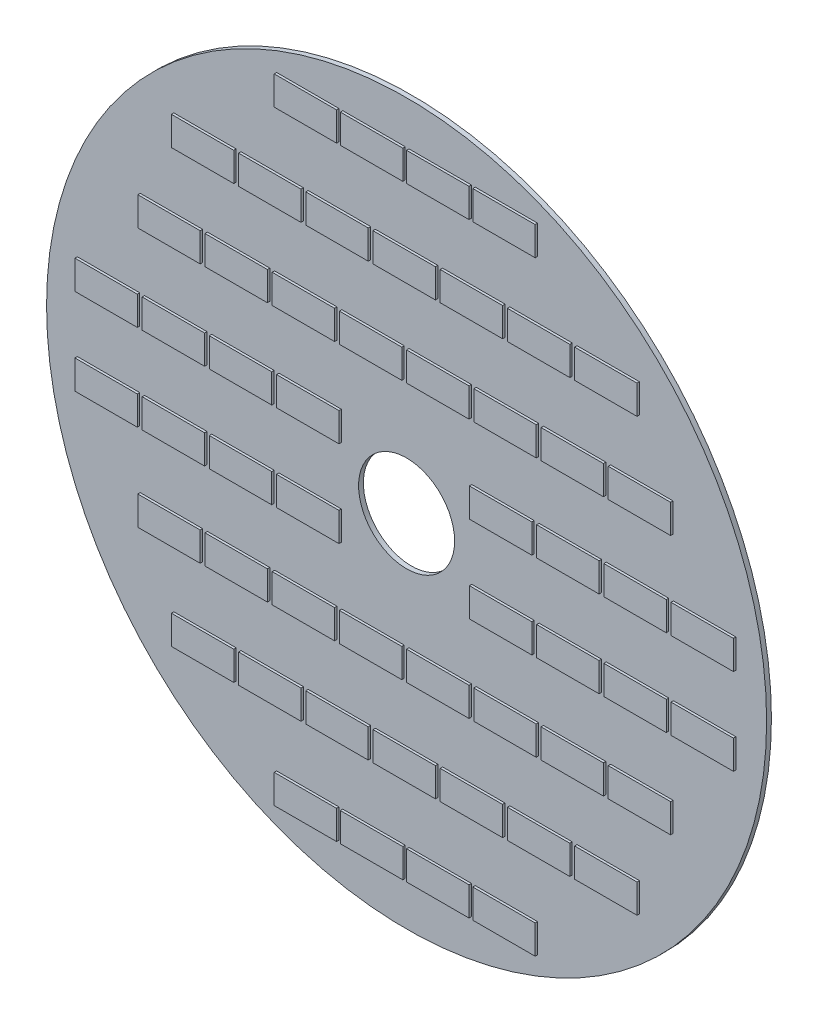
SolidWorks part; units mm, degrees
ref_plane "前视基准面" through (0, 0, 0) normal (0, 0, 1) x (1, 0, 0)
ref_plane "上视基准面" through (0, 0, 0) normal (0, 1, 0) x (1, 0, 0)
ref_plane "右视基准面" through (0, 0, 0) normal (1, 0, 0) x (0, 0, -1)
other "Configuration Table"
sketch "草图1" plane through (0, 0, 0) normal (0, 0, 1) x (1, 0, 0)
  line L5 (100, 90) -> (230, 90)
  line L6 (100, 90) -> (100, 30)
  line L8 (100, 30) -> (230, 30)
  line L12 (230, 90) -> (230, 30)
  line L14 (100, 90) -> (230, 30) construction
  line L18 (100, 30) -> (230, 90) construction
  line L24 (-1658.199, 0) -> (1658.199, 0) construction
  line L26 (0, 1113.9389) -> (0, -1113.9389) construction
  line L50 (300, 90) -> (430, 90)
  line L53 (300, 90) -> (300, 30)
  line L57 (300, 30) -> (430, 30)
  line L58 (430, 90) -> (430, 30)
  line L59 (300, 90) -> (430, 30) construction
  line L60 (300, 30) -> (430, 90) construction
  line L61 (37.3566, 180) -> (37.3566, 120)
  line L62 (237.3566, 120) -> (367.3566, 120)
  line L63 (237.3566, 180) -> (367.3566, 120) construction
  line L64 (37.3566, 120) -> (167.3566, 180) construction
  line L65 (237.3566, 180) -> (237.3566, 120)
  line L66 (367.3566, 180) -> (367.3566, 120)
  line L67 (37.3566, 180) -> (167.3566, 180)
  line L68 (37.3566, 180) -> (167.3566, 120) construction
  line L69 (237.3566, 180) -> (367.3566, 180)
  line L70 (237.3566, 120) -> (367.3566, 180) construction
  line L71 (37.3566, 120) -> (167.3566, 120)
  line L72 (167.3566, 180) -> (167.3566, 120)
  line L83 (37.3566, 364.2375) -> (37.3566, 304.2375)
  line L84 (237.3566, 304.2375) -> (367.3566, 304.2375)
  line L91 (133.7252, 270) -> (133.7252, 210)
  line L92 (333.7252, 210) -> (463.7252, 210)
  line L93 (333.7252, 270) -> (463.7252, 210) construction
  line L94 (133.7252, 210) -> (266.6142, 270) construction
  line L95 (333.7252, 270) -> (333.7252, 210)
  line L96 (463.7252, 270) -> (463.7252, 210)
  line L97 (133.7252, 270) -> (266.6142, 270)
  line L98 (133.7252, 270) -> (266.6142, 210) construction
  line L99 (333.7252, 270) -> (463.7252, 270)
  line L100 (333.7252, 210) -> (463.7252, 270) construction
  line L101 (133.7252, 210) -> (266.6142, 210)
  line L102 (266.6142, 270) -> (266.6142, 210)
  line L103 (-65, 274.2375) -> (-65, 210)
  line L104 (-65, 274.2375) -> (65, 274.2375)
  line L105 (-65, 210) -> (65, 210)
  line L106 (65, 274.2375) -> (65, 210)
  line L107 (-65, 210) -> (65, 274.2375) construction
  line L108 (-65, 274.2375) -> (65, 210) construction
  line L109 (-264.8303, 270) -> (-264.8303, 210)
  line L110 (-264.8303, 270) -> (-134.8303, 270)
  line L111 (-264.8303, 210) -> (-134.8303, 210)
  line L112 (-134.8303, 270) -> (-134.8303, 210)
  line L113 (-264.8303, 210) -> (-134.8303, 270) construction
  line L114 (-264.8303, 270) -> (-134.8303, 210) construction
  line L115 (-464.8303, 270) -> (-464.8303, 210)
  line L116 (-464.8303, 270) -> (-334.8303, 270)
  line L117 (-464.8303, 210) -> (-334.8303, 210)
  line L118 (-334.8303, 270) -> (-334.8303, 210)
  line L119 (-464.8303, 210) -> (-334.8303, 270) construction
  line L120 (-464.8303, 270) -> (-334.8303, 210) construction
  line L122 (237.3566, 364.2375) -> (237.3566, 304.2375)
  line L123 (367.3566, 364.2375) -> (367.3566, 304.2375)
  line L125 (37.3566, 364.2375) -> (167.3566, 364.2375)
  line L127 (237.3566, 364.2375) -> (367.3566, 364.2375)
  line L128 (37.3566, 304.2375) -> (167.3566, 304.2375)
  line L129 (167.3566, 364.2375) -> (167.3566, 304.2375)
  line L139 (237.3566, 364.2375) -> (367.3566, 304.2375) construction
  line L140 (37.3566, 304.2375) -> (167.3566, 364.2375) construction
  line L141 (37.3566, 364.2375) -> (167.3566, 304.2375) construction
  line L142 (237.3566, 304.2375) -> (367.3566, 364.2375) construction
  line L143 (37.3566, 450) -> (37.3566, 390)
  line L144 (237.3566, 390) -> (367.3566, 390)
  line L145 (237.3566, 450) -> (237.3566, 390)
  line L146 (367.3566, 450) -> (367.3566, 390)
  line L147 (37.3566, 450) -> (167.3566, 450)
  line L148 (237.3566, 450) -> (367.3566, 450)
  line L149 (37.3566, 390) -> (167.3566, 390)
  line L150 (167.3566, 450) -> (167.3566, 390)
  line L151 (237.3566, 450) -> (367.3566, 390) construction
  line L152 (37.3566, 390) -> (167.3566, 450) construction
  line L153 (37.3566, 450) -> (167.3566, 390) construction
  line L154 (237.3566, 390) -> (367.3566, 450) construction
  line L155 (37.3566, 535.7625) -> (37.3566, 475.7625)
  line L156 (237.3566, 475.7625) -> (367.3566, 475.7625)
  line L157 (237.3566, 535.7625) -> (237.3566, 475.7625)
  line L158 (367.3566, 535.7625) -> (367.3566, 475.7625)
  line L159 (37.3566, 535.7625) -> (167.3566, 535.7625)
  line L160 (237.3566, 535.7625) -> (367.3566, 535.7625)
  line L161 (37.3566, 475.7625) -> (167.3566, 475.7625)
  line L162 (167.3566, 535.7625) -> (167.3566, 475.7625)
  line L163 (237.3566, 535.7625) -> (367.3566, 475.7625) construction
  line L164 (37.3566, 475.7625) -> (167.3566, 535.7625) construction
  line L165 (37.3566, 535.7625) -> (167.3566, 475.7625) construction
  line L166 (237.3566, 475.7625) -> (367.3566, 535.7625) construction
  line L167 (-264.8303, 565.7625) -> (-134.8303, 625.7625) construction
  line L168 (133.7252, 565.7625) -> (266.6142, 565.7625)
  line L169 (-65, 565.7625) -> (65, 625.7625) construction
  line L170 (-65, 625.7625) -> (-65, 565.7625)
  line L171 (-264.8303, 625.7625) -> (-264.8303, 565.7625)
  line L172 (-134.8303, 625.7625) -> (-134.8303, 565.7625)
  line L173 (133.7252, 625.7625) -> (266.6142, 625.7625)
  line L174 (133.7252, 625.7625) -> (266.6142, 565.7625) construction
  line L175 (65, 625.7625) -> (65, 565.7625)
  line L176 (-264.8303, 625.7625) -> (-134.8303, 565.7625) construction
  line L177 (133.7252, 625.7625) -> (133.7252, 565.7625)
  line L178 (-65, 625.7625) -> (65, 625.7625)
  line L179 (-65, 565.7625) -> (65, 565.7625)
  line L180 (-264.8303, 565.7625) -> (-134.8303, 565.7625)
  line L181 (133.7252, 565.7625) -> (266.6142, 625.7625) construction
  line L182 (266.6142, 625.7625) -> (266.6142, 565.7625)
  line L183 (-264.8303, 625.7625) -> (-134.8303, 625.7625)
  line L184 (-65, 625.7625) -> (65, 565.7625) construction
  line L185 (-300, 90) -> (-300, 30)
  line L186 (-300, 30) -> (-430, 30)
  line L187 (-430, 90) -> (-430, 30)
  line L188 (-300, 90) -> (-430, 90)
  line L189 (-100, 30) -> (-230, 30)
  line L190 (-230, 90) -> (-230, 30)
  line L191 (-100, 90) -> (-230, 90)
  line L192 (-100, 90) -> (-100, 30)
  line L193 (-37.3566, 180) -> (-167.3566, 180)
  line L194 (-167.3566, 180) -> (-167.3566, 120)
  line L195 (-37.3566, 120) -> (-167.3566, 120)
  line L196 (-37.3566, 180) -> (-37.3566, 120)
  line L197 (-237.3566, 180) -> (-237.3566, 120)
  line L198 (-237.3566, 180) -> (-367.3566, 180)
  line L199 (-367.3566, 180) -> (-367.3566, 120)
  line L200 (-237.3566, 120) -> (-367.3566, 120)
  line L201 (-237.3566, 475.7625) -> (-367.3566, 535.7625) construction
  line L202 (-37.3566, 535.7625) -> (-167.3566, 475.7625) construction
  line L203 (-37.3566, 475.7625) -> (-167.3566, 535.7625) construction
  line L204 (-237.3566, 535.7625) -> (-367.3566, 475.7625) construction
  line L205 (-237.3566, 390) -> (-367.3566, 450) construction
  line L206 (-37.3566, 450) -> (-167.3566, 390) construction
  line L207 (-37.3566, 390) -> (-167.3566, 450) construction
  line L208 (-237.3566, 450) -> (-367.3566, 390) construction
  line L209 (-237.3566, 304.2375) -> (-367.3566, 364.2375) construction
  line L210 (-37.3566, 364.2375) -> (-167.3566, 304.2375) construction
  line L211 (-37.3566, 304.2375) -> (-167.3566, 364.2375) construction
  line L212 (-237.3566, 364.2375) -> (-367.3566, 304.2375) construction
  line L213 (-167.3566, 535.7625) -> (-167.3566, 475.7625)
  line L214 (-37.3566, 475.7625) -> (-167.3566, 475.7625)
  line L215 (-237.3566, 535.7625) -> (-367.3566, 535.7625)
  line L216 (-37.3566, 535.7625) -> (-167.3566, 535.7625)
  line L217 (-367.3566, 535.7625) -> (-367.3566, 475.7625)
  line L218 (-237.3566, 535.7625) -> (-237.3566, 475.7625)
  line L219 (-237.3566, 475.7625) -> (-367.3566, 475.7625)
  line L220 (-37.3566, 535.7625) -> (-37.3566, 475.7625)
  line L221 (-167.3566, 450) -> (-167.3566, 390)
  line L222 (-37.3566, 390) -> (-167.3566, 390)
  line L223 (-237.3566, 450) -> (-367.3566, 450)
  line L224 (-37.3566, 450) -> (-167.3566, 450)
  line L225 (-367.3566, 450) -> (-367.3566, 390)
  line L226 (-237.3566, 450) -> (-237.3566, 390)
  line L227 (-237.3566, 390) -> (-367.3566, 390)
  line L228 (-37.3566, 450) -> (-37.3566, 390)
  line L229 (-167.3566, 364.2375) -> (-167.3566, 304.2375)
  line L230 (-37.3566, 304.2375) -> (-167.3566, 304.2375)
  line L231 (-237.3566, 364.2375) -> (-367.3566, 364.2375)
  line L232 (-37.3566, 364.2375) -> (-167.3566, 364.2375)
  line L233 (-367.3566, 364.2375) -> (-367.3566, 304.2375)
  line L234 (-237.3566, 364.2375) -> (-237.3566, 304.2375)
  line L235 (-237.3566, 304.2375) -> (-367.3566, 304.2375)
  line L236 (-37.3566, 364.2375) -> (-37.3566, 304.2375)
  line L237 (-237.3566, -364.2375) -> (-367.3566, -304.2375) construction
  line L238 (-37.3566, -304.2375) -> (-167.3566, -364.2375) construction
  line L239 (-37.3566, -364.2375) -> (-167.3566, -304.2375) construction
  line L240 (-237.3566, -304.2375) -> (-367.3566, -364.2375) construction
  line L241 (-237.3566, -450) -> (-367.3566, -390) construction
  line L242 (-37.3566, -390) -> (-167.3566, -450) construction
  line L243 (-37.3566, -450) -> (-167.3566, -390) construction
  line L244 (-237.3566, -390) -> (-367.3566, -450) construction
  line L245 (-237.3566, -535.7625) -> (-367.3566, -475.7625) construction
  line L246 (-37.3566, -475.7625) -> (-167.3566, -535.7625) construction
  line L247 (-37.3566, -535.7625) -> (-167.3566, -475.7625) construction
  line L248 (-237.3566, -475.7625) -> (-367.3566, -535.7625) construction
  line L249 (-65, -625.7625) -> (65, -565.7625) construction
  line L250 (133.7252, -565.7625) -> (266.6142, -625.7625) construction
  line L251 (-264.8303, -625.7625) -> (-134.8303, -565.7625) construction
  line L252 (133.7252, -625.7625) -> (266.6142, -565.7625) construction
  line L253 (-65, -565.7625) -> (65, -625.7625) construction
  line L254 (-264.8303, -565.7625) -> (-134.8303, -625.7625) construction
  line L255 (237.3566, -475.7625) -> (367.3566, -535.7625) construction
  line L256 (37.3566, -535.7625) -> (167.3566, -475.7625) construction
  line L257 (37.3566, -475.7625) -> (167.3566, -535.7625) construction
  line L258 (237.3566, -535.7625) -> (367.3566, -475.7625) construction
  line L259 (237.3566, -390) -> (367.3566, -450) construction
  line L260 (37.3566, -450) -> (167.3566, -390) construction
  line L261 (37.3566, -390) -> (167.3566, -450) construction
  line L262 (237.3566, -450) -> (367.3566, -390) construction
  line L263 (237.3566, -304.2375) -> (367.3566, -364.2375) construction
  line L264 (37.3566, -364.2375) -> (167.3566, -304.2375) construction
  line L265 (37.3566, -304.2375) -> (167.3566, -364.2375) construction
  line L266 (237.3566, -364.2375) -> (367.3566, -304.2375) construction
  line L267 (-464.8303, -270) -> (-334.8303, -210) construction
  line L268 (-464.8303, -210) -> (-334.8303, -270) construction
  line L269 (-264.8303, -270) -> (-134.8303, -210) construction
  line L270 (-264.8303, -210) -> (-134.8303, -270) construction
  line L271 (-65, -274.2375) -> (65, -210) construction
  line L272 (-65, -210) -> (65, -274.2375) construction
  line L273 (333.7252, -210) -> (463.7252, -270) construction
  line L274 (133.7252, -270) -> (266.6142, -210) construction
  line L275 (133.7252, -210) -> (266.6142, -270) construction
  line L276 (333.7252, -270) -> (463.7252, -210) construction
  line L277 (237.3566, -120) -> (367.3566, -180) construction
  line L278 (37.3566, -180) -> (167.3566, -120) construction
  line L279 (37.3566, -120) -> (167.3566, -180) construction
  line L280 (237.3566, -180) -> (367.3566, -120) construction
  line L281 (300, -30) -> (430, -90) construction
  line L282 (300, -90) -> (430, -30) construction
  line L283 (100, -30) -> (230, -90) construction
  line L284 (100, -90) -> (230, -30) construction
  line L285 (-37.3566, -364.2375) -> (-37.3566, -304.2375)
  line L286 (-237.3566, -304.2375) -> (-367.3566, -304.2375)
  line L287 (-237.3566, -364.2375) -> (-237.3566, -304.2375)
  line L288 (-367.3566, -364.2375) -> (-367.3566, -304.2375)
  line L289 (-37.3566, -364.2375) -> (-167.3566, -364.2375)
  line L290 (-237.3566, -364.2375) -> (-367.3566, -364.2375)
  line L291 (-37.3566, -304.2375) -> (-167.3566, -304.2375)
  line L292 (-167.3566, -364.2375) -> (-167.3566, -304.2375)
  line L293 (-37.3566, -450) -> (-37.3566, -390)
  line L294 (-237.3566, -390) -> (-367.3566, -390)
  line L295 (-237.3566, -450) -> (-237.3566, -390)
  line L296 (-367.3566, -450) -> (-367.3566, -390)
  line L297 (-37.3566, -450) -> (-167.3566, -450)
  line L298 (-237.3566, -450) -> (-367.3566, -450)
  line L299 (-37.3566, -390) -> (-167.3566, -390)
  line L300 (-167.3566, -450) -> (-167.3566, -390)
  line L301 (-37.3566, -535.7625) -> (-37.3566, -475.7625)
  line L302 (-237.3566, -475.7625) -> (-367.3566, -475.7625)
  line L303 (-237.3566, -535.7625) -> (-237.3566, -475.7625)
  line L304 (-367.3566, -535.7625) -> (-367.3566, -475.7625)
  line L305 (-37.3566, -535.7625) -> (-167.3566, -535.7625)
  line L306 (-237.3566, -535.7625) -> (-367.3566, -535.7625)
  line L307 (-37.3566, -475.7625) -> (-167.3566, -475.7625)
  line L308 (-167.3566, -535.7625) -> (-167.3566, -475.7625)
  line L309 (-237.3566, -120) -> (-367.3566, -120)
  line L310 (-367.3566, -180) -> (-367.3566, -120)
  line L311 (-237.3566, -180) -> (-367.3566, -180)
  line L312 (-237.3566, -180) -> (-237.3566, -120)
  line L313 (-37.3566, -180) -> (-37.3566, -120)
  line L314 (-37.3566, -120) -> (-167.3566, -120)
  line L315 (-167.3566, -180) -> (-167.3566, -120)
  line L316 (-37.3566, -180) -> (-167.3566, -180)
  line L317 (-100, -90) -> (-100, -30)
  line L318 (-100, -90) -> (-230, -90)
  line L319 (-230, -90) -> (-230, -30)
  line L320 (-100, -30) -> (-230, -30)
  line L321 (-300, -90) -> (-430, -90)
  line L322 (-430, -90) -> (-430, -30)
  line L323 (-300, -30) -> (-430, -30)
  line L324 (-300, -90) -> (-300, -30)
  line L325 (-264.8303, -625.7625) -> (-134.8303, -625.7625)
  line L326 (266.6142, -625.7625) -> (266.6142, -565.7625)
  line L327 (-264.8303, -565.7625) -> (-134.8303, -565.7625)
  line L328 (-65, -565.7625) -> (65, -565.7625)
  line L329 (-65, -625.7625) -> (65, -625.7625)
  line L330 (133.7252, -625.7625) -> (133.7252, -565.7625)
  line L331 (65, -625.7625) -> (65, -565.7625)
  line L332 (133.7252, -625.7625) -> (266.6142, -625.7625)
  line L333 (-134.8303, -625.7625) -> (-134.8303, -565.7625)
  line L334 (-264.8303, -625.7625) -> (-264.8303, -565.7625)
  line L335 (-65, -625.7625) -> (-65, -565.7625)
  line L336 (133.7252, -565.7625) -> (266.6142, -565.7625)
  line L337 (167.3566, -535.7625) -> (167.3566, -475.7625)
  line L338 (37.3566, -475.7625) -> (167.3566, -475.7625)
  line L339 (237.3566, -535.7625) -> (367.3566, -535.7625)
  line L340 (37.3566, -535.7625) -> (167.3566, -535.7625)
  line L341 (367.3566, -535.7625) -> (367.3566, -475.7625)
  line L342 (237.3566, -535.7625) -> (237.3566, -475.7625)
  line L343 (237.3566, -475.7625) -> (367.3566, -475.7625)
  line L344 (37.3566, -535.7625) -> (37.3566, -475.7625)
  line L345 (167.3566, -450) -> (167.3566, -390)
  line L346 (37.3566, -390) -> (167.3566, -390)
  line L347 (237.3566, -450) -> (367.3566, -450)
  line L348 (37.3566, -450) -> (167.3566, -450)
  line L349 (367.3566, -450) -> (367.3566, -390)
  line L350 (237.3566, -450) -> (237.3566, -390)
  line L351 (237.3566, -390) -> (367.3566, -390)
  line L352 (37.3566, -450) -> (37.3566, -390)
  line L353 (167.3566, -364.2375) -> (167.3566, -304.2375)
  line L354 (37.3566, -304.2375) -> (167.3566, -304.2375)
  line L355 (237.3566, -364.2375) -> (367.3566, -364.2375)
  line L356 (37.3566, -364.2375) -> (167.3566, -364.2375)
  line L357 (367.3566, -364.2375) -> (367.3566, -304.2375)
  line L358 (237.3566, -364.2375) -> (237.3566, -304.2375)
  line L359 (-334.8303, -270) -> (-334.8303, -210)
  line L360 (-464.8303, -210) -> (-334.8303, -210)
  line L361 (-464.8303, -270) -> (-334.8303, -270)
  line L362 (-464.8303, -270) -> (-464.8303, -210)
  line L363 (-134.8303, -270) -> (-134.8303, -210)
  line L364 (-264.8303, -210) -> (-134.8303, -210)
  line L365 (-264.8303, -270) -> (-134.8303, -270)
  line L366 (-264.8303, -270) -> (-264.8303, -210)
  line L367 (65, -274.2375) -> (65, -210)
  line L368 (-65, -210) -> (65, -210)
  line L369 (-65, -274.2375) -> (65, -274.2375)
  line L370 (-65, -274.2375) -> (-65, -210)
  line L371 (266.6142, -270) -> (266.6142, -210)
  line L372 (133.7252, -210) -> (266.6142, -210)
  line L373 (333.7252, -270) -> (463.7252, -270)
  line L374 (133.7252, -270) -> (266.6142, -270)
  line L375 (463.7252, -270) -> (463.7252, -210)
  line L376 (333.7252, -270) -> (333.7252, -210)
  line L377 (333.7252, -210) -> (463.7252, -210)
  line L378 (133.7252, -270) -> (133.7252, -210)
  line L379 (237.3566, -304.2375) -> (367.3566, -304.2375)
  line L380 (37.3566, -364.2375) -> (37.3566, -304.2375)
  line L381 (167.3566, -180) -> (167.3566, -120)
  line L382 (37.3566, -120) -> (167.3566, -120)
  line L383 (237.3566, -180) -> (367.3566, -180)
  line L384 (37.3566, -180) -> (167.3566, -180)
  line L385 (367.3566, -180) -> (367.3566, -120)
  line L386 (237.3566, -180) -> (237.3566, -120)
  line L387 (237.3566, -120) -> (367.3566, -120)
  line L388 (37.3566, -180) -> (37.3566, -120)
  line L389 (430, -90) -> (430, -30)
  line L390 (300, -30) -> (430, -30)
  line L391 (300, -90) -> (300, -30)
  line L392 (300, -90) -> (430, -90)
  line L393 (230, -90) -> (230, -30)
  line L394 (100, -30) -> (230, -30)
  line L395 (100, -90) -> (100, -30)
  line L396 (100, -90) -> (230, -90)
  line L397 (-65, 715.7625) -> (65, 715.7625)
  line L398 (-65, 715.7625) -> (65, 655.7625) construction
  line L399 (65, 715.7625) -> (65, 655.7625)
  line L400 (-65, 655.7625) -> (65, 715.7625) construction
  line L401 (-65, 715.7625) -> (-65, 655.7625)
  line L402 (-65, 655.7625) -> (65, 655.7625)
  line L403 (-65, -655.7625) -> (65, -715.7625) construction
  line L404 (-65, -715.7625) -> (65, -655.7625) construction
  line L405 (-65, -655.7625) -> (65, -655.7625)
  line L406 (-65, -715.7625) -> (-65, -655.7625)
  line L407 (65, -715.7625) -> (65, -655.7625)
  line L408 (-65, -715.7625) -> (65, -715.7625)
  circle A0 centre (0, 0) radius 750 construction
  point P0 (165, 60)
  point P5 (102.3566, 150)
  point P7 (365, 60)
  point P16 (302.3566, 192.8005)
  point P24 (200.1697, 595.7625)
  point P26 (200.1697, 240)
  point P29 (102.3566, 334.2375)
  point P39 (102.3566, 420)
  point P47 (0, 274.2375)
  point P70 (102.3566, 505.7625)
  point P80 (302.3566, 462.8005)
  point P81 (302.3566, 377.038)
  point P132 (-102.3566, 505.7625)
  point P133 (-102.3566, 420)
  point P134 (-102.3566, 334.2375)
  point P247 (-102.3566, -334.2375)
  point P248 (-102.3566, -420)
  point P249 (-102.3566, -505.7625)
  point P250 (102.3566, -505.7625)
  point P251 (102.3566, -420)
  point P252 (102.3566, -334.2375)
  point P253 (200.1697, -240)
  point P254 (200.1697, -595.7625)
  point P255 (302.3566, -192.8005)
  point P256 (365, -60)
  point P257 (102.3566, -150)
  point P258 (165, -60)
  dimension "D3" = 100
  dimension "D1" = 2
  dimension "D2" = 30
  dimension "D4" = 30
  dimension "D5" = 60
  dimension "D6" = 130
  dimension "D7" = 70
  dimension "D8" = 70
  dimension "D9" = 2
  dimension "D10" = 3
  dimension "D11" = 130
  dimension "D12" = 60
  dimension "D13" = 30
  dimension "D14" = 60
  dimension "D15" = 30
sketch "草图2" plane through (0, 0, 0) normal (0, 0, 1) x (1, 0, 0)
  circle A0 centre (0, 0) radius 750
  circle A1 centre (0, 0) radius 100
  dimension "D1" = 1500
  dimension "D2" = 200
extrude "凸台-拉伸1" add sketch "草图2" along normal blind 10
sketch "草图3" plane through (0, 0, 0) normal (0, 0, 1) x (1, 0, 0)
  line L0 (-1673.2224, 0) -> (1673.2224, 0) construction
  line L2 (135.9057, 120) -> (265.9057, 120)
  line L3 (0, -869.8968) -> (0, 1064.1184) construction
  line L4 (135.9057, 120) -> (135.9057, 60)
  line L5 (135.9057, 60) -> (265.9057, 60)
  line L6 (265.9057, 120) -> (265.9057, 60)
  line L18 (275.9057, 120) -> (275.9057, 60)
  line L19 (275.9057, 120) -> (405.9057, 120)
  line L20 (405.9057, 120) -> (405.9057, 60)
  line L21 (275.9057, 60) -> (405.9057, 60)
  line L22 (415.9057, 120) -> (415.9057, 60)
  line L23 (415.9057, 120) -> (545.9057, 120)
  line L24 (545.9057, 120) -> (545.9057, 60)
  line L25 (415.9057, 60) -> (545.9057, 60)
  line L26 (555.9057, 120) -> (555.9057, 60)
  line L27 (555.9057, 120) -> (685.9057, 120)
  line L28 (685.9057, 120) -> (685.9057, 60)
  line L29 (555.9057, 60) -> (685.9057, 60)
  line L30 (145, 300) -> (145, 240)
  line L31 (-555.9057, 60) -> (-685.9057, 60)
  line L32 (-685.9057, 120) -> (-685.9057, 60)
  line L33 (-555.9057, 120) -> (-685.9057, 120)
  line L34 (-555.9057, 120) -> (-555.9057, 60)
  line L35 (-415.9057, 60) -> (-545.9057, 60)
  line L36 (-545.9057, 120) -> (-545.9057, 60)
  line L37 (-415.9057, 120) -> (-545.9057, 120)
  line L38 (-415.9057, 120) -> (-415.9057, 60)
  line L39 (-275.9057, 60) -> (-405.9057, 60)
  line L40 (-405.9057, 120) -> (-405.9057, 60)
  line L41 (-275.9057, 120) -> (-405.9057, 120)
  line L42 (-275.9057, 120) -> (-275.9057, 60)
  line L43 (-265.9057, 120) -> (-265.9057, 60)
  line L44 (-135.9057, 60) -> (-265.9057, 60)
  line L45 (-135.9057, 120) -> (-135.9057, 60)
  line L46 (-135.9057, 120) -> (-265.9057, 120)
  line L47 (145, 300) -> (275, 300)
  line L48 (5, 300) -> (135, 300)
  line L49 (5, 300) -> (5, 240)
  line L50 (5, 240) -> (135, 240)
  line L51 (135, 300) -> (135, 240)
  line L52 (275, 300) -> (275, 240)
  line L53 (145, 240) -> (275, 240)
  line L54 (285, 300) -> (285, 240)
  line L55 (285, 300) -> (415, 300)
  line L56 (415, 300) -> (415, 240)
  line L57 (285, 240) -> (415, 240)
  line L58 (425, 300) -> (425, 240)
  line L59 (425, 300) -> (555, 300)
  line L60 (555, 300) -> (555, 240)
  line L61 (425, 240) -> (555, 240)
  line L62 (-425, 240) -> (-555, 240)
  line L63 (-555, 300) -> (-555, 240)
  line L64 (-425, 300) -> (-555, 300)
  line L65 (-425, 300) -> (-425, 240)
  line L66 (-285, 240) -> (-415, 240)
  line L67 (-415, 300) -> (-415, 240)
  line L68 (-285, 300) -> (-415, 300)
  line L69 (-285, 300) -> (-285, 240)
  line L70 (-145, 240) -> (-275, 240)
  line L71 (-275, 300) -> (-275, 240)
  line L72 (-135, 300) -> (-135, 240)
  line L73 (-5, 240) -> (-135, 240)
  line L74 (-5, 300) -> (-5, 240)
  line L75 (-5, 300) -> (-135, 300)
  line L76 (-145, 300) -> (-275, 300)
  line L77 (-145, 300) -> (-145, 240)
  line L78 (75, 480) -> (205, 480)
  line L79 (-65, 480) -> (65, 480)
  line L80 (-65, 480) -> (-65, 420)
  line L81 (-65, 420) -> (65, 420)
  line L82 (65, 480) -> (65, 420)
  line L83 (75, 480) -> (75, 420)
  line L84 (75, 420) -> (205, 420)
  line L85 (205, 480) -> (205, 420)
  line L86 (215, 480) -> (345, 480)
  line L87 (215, 480) -> (215, 420)
  line L88 (215, 420) -> (345, 420)
  line L89 (345, 480) -> (345, 420)
  line L90 (355, 480) -> (485, 480)
  line L91 (355, 480) -> (355, 420)
  line L92 (355, 420) -> (485, 420)
  line L93 (485, 480) -> (485, 420)
  line L94 (-485, 480) -> (-485, 420)
  line L95 (-355, 420) -> (-485, 420)
  line L96 (-355, 480) -> (-355, 420)
  line L97 (-355, 480) -> (-485, 480)
  line L98 (-345, 480) -> (-345, 420)
  line L99 (-215, 420) -> (-345, 420)
  line L100 (-215, 480) -> (-215, 420)
  line L101 (-215, 480) -> (-345, 480)
  line L102 (-205, 480) -> (-205, 420)
  line L103 (-75, 420) -> (-205, 420)
  line L104 (-75, 480) -> (-75, 420)
  line L105 (-75, 480) -> (-205, 480)
  line L106 (-132.9073, 660) -> (-132.9073, 600)
  line L107 (-270.8146, 660) -> (-140.8146, 660)
  line L108 (-270.8146, 660) -> (-270.8146, 600)
  line L109 (-270.8146, 600) -> (-140.8146, 600)
  line L110 (-140.8146, 660) -> (-140.8146, 600)
  line L111 (-132.9073, 660) -> (-2.9073, 660)
  line L112 (-2.9073, 660) -> (-2.9073, 600)
  line L113 (-132.9073, 600) -> (-2.9073, 600)
  line L114 (5, 660) -> (5, 600)
  line L115 (5, 660) -> (135, 660)
  line L116 (135, 660) -> (135, 600)
  line L117 (5, 600) -> (135, 600)
  line L118 (142.9073, 660) -> (142.9073, 600)
  line L119 (142.9073, 660) -> (272.9073, 660)
  line L120 (272.9073, 660) -> (272.9073, 600)
  line L121 (142.9073, 600) -> (272.9073, 600)
  line L122 (142.9073, -600) -> (272.9073, -600)
  line L123 (272.9073, -660) -> (272.9073, -600)
  line L124 (142.9073, -660) -> (272.9073, -660)
  line L125 (142.9073, -660) -> (142.9073, -600)
  line L126 (5, -600) -> (135, -600)
  line L127 (135, -660) -> (135, -600)
  line L128 (5, -660) -> (135, -660)
  line L129 (5, -660) -> (5, -600)
  line L130 (-132.9073, -600) -> (-2.9073, -600)
  line L131 (-2.9073, -660) -> (-2.9073, -600)
  line L132 (-132.9073, -660) -> (-2.9073, -660)
  line L133 (-140.8146, -660) -> (-140.8146, -600)
  line L134 (-270.8146, -600) -> (-140.8146, -600)
  line L135 (-270.8146, -660) -> (-270.8146, -600)
  line L136 (-270.8146, -660) -> (-140.8146, -660)
  line L137 (-132.9073, -660) -> (-132.9073, -600)
  line L138 (-75, -480) -> (-205, -480)
  line L139 (-75, -480) -> (-75, -420)
  line L140 (-75, -420) -> (-205, -420)
  line L141 (-205, -480) -> (-205, -420)
  line L142 (-215, -480) -> (-345, -480)
  line L143 (-215, -480) -> (-215, -420)
  line L144 (-215, -420) -> (-345, -420)
  line L145 (-345, -480) -> (-345, -420)
  line L146 (-355, -480) -> (-485, -480)
  line L147 (-355, -480) -> (-355, -420)
  line L148 (-355, -420) -> (-485, -420)
  line L149 (-485, -480) -> (-485, -420)
  line L150 (485, -480) -> (485, -420)
  line L151 (355, -420) -> (485, -420)
  line L152 (355, -480) -> (355, -420)
  line L153 (355, -480) -> (485, -480)
  line L154 (345, -480) -> (345, -420)
  line L155 (215, -420) -> (345, -420)
  line L156 (215, -480) -> (215, -420)
  line L157 (215, -480) -> (345, -480)
  line L158 (205, -480) -> (205, -420)
  line L159 (75, -420) -> (205, -420)
  line L160 (75, -480) -> (75, -420)
  line L161 (65, -480) -> (65, -420)
  line L162 (-65, -420) -> (65, -420)
  line L163 (-65, -480) -> (-65, -420)
  line L164 (-65, -480) -> (65, -480)
  line L165 (75, -480) -> (205, -480)
  line L166 (-145, -300) -> (-145, -240)
  line L167 (-145, -300) -> (-275, -300)
  line L168 (-5, -300) -> (-135, -300)
  line L169 (-5, -300) -> (-5, -240)
  line L170 (-5, -240) -> (-135, -240)
  line L171 (-135, -300) -> (-135, -240)
  line L172 (-275, -300) -> (-275, -240)
  line L173 (-145, -240) -> (-275, -240)
  line L174 (-285, -300) -> (-285, -240)
  line L175 (-285, -300) -> (-415, -300)
  line L176 (-415, -300) -> (-415, -240)
  line L177 (-285, -240) -> (-415, -240)
  line L178 (-425, -300) -> (-425, -240)
  line L179 (-425, -300) -> (-555, -300)
  line L180 (-555, -300) -> (-555, -240)
  line L181 (-425, -240) -> (-555, -240)
  line L182 (425, -240) -> (555, -240)
  line L183 (555, -300) -> (555, -240)
  line L184 (425, -300) -> (555, -300)
  line L185 (425, -300) -> (425, -240)
  line L186 (285, -240) -> (415, -240)
  line L187 (415, -300) -> (415, -240)
  line L188 (285, -300) -> (415, -300)
  line L189 (285, -300) -> (285, -240)
  line L190 (145, -240) -> (275, -240)
  line L191 (275, -300) -> (275, -240)
  line L192 (135, -300) -> (135, -240)
  line L193 (5, -240) -> (135, -240)
  line L194 (5, -300) -> (5, -240)
  line L195 (5, -300) -> (135, -300)
  line L196 (145, -300) -> (275, -300)
  line L197 (-135.9057, -120) -> (-265.9057, -120)
  line L198 (-135.9057, -120) -> (-135.9057, -60)
  line L199 (-135.9057, -60) -> (-265.9057, -60)
  line L200 (-265.9057, -120) -> (-265.9057, -60)
  line L201 (-275.9057, -120) -> (-275.9057, -60)
  line L202 (-275.9057, -120) -> (-405.9057, -120)
  line L203 (-405.9057, -120) -> (-405.9057, -60)
  line L204 (-275.9057, -60) -> (-405.9057, -60)
  line L205 (-415.9057, -120) -> (-415.9057, -60)
  line L206 (-415.9057, -120) -> (-545.9057, -120)
  line L207 (-545.9057, -120) -> (-545.9057, -60)
  line L208 (-415.9057, -60) -> (-545.9057, -60)
  line L209 (-555.9057, -120) -> (-555.9057, -60)
  line L210 (-555.9057, -120) -> (-685.9057, -120)
  line L211 (-685.9057, -120) -> (-685.9057, -60)
  line L212 (-555.9057, -60) -> (-685.9057, -60)
  line L213 (145, -300) -> (145, -240)
  line L214 (555.9057, -60) -> (685.9057, -60)
  line L215 (685.9057, -120) -> (685.9057, -60)
  line L216 (555.9057, -120) -> (685.9057, -120)
  line L217 (555.9057, -120) -> (555.9057, -60)
  line L218 (415.9057, -60) -> (545.9057, -60)
  line L219 (545.9057, -120) -> (545.9057, -60)
  line L220 (415.9057, -120) -> (545.9057, -120)
  line L221 (415.9057, -120) -> (415.9057, -60)
  line L222 (275.9057, -60) -> (405.9057, -60)
  line L223 (405.9057, -120) -> (405.9057, -60)
  line L224 (275.9057, -120) -> (405.9057, -120)
  line L225 (275.9057, -120) -> (275.9057, -60)
  line L226 (265.9057, -120) -> (265.9057, -60)
  line L227 (135.9057, -60) -> (265.9057, -60)
  line L228 (135.9057, -120) -> (135.9057, -60)
  line L229 (135.9057, -120) -> (265.9057, -120)
  point P4 (0, 0)
  point P6 (0, 0)
  point P75 (0, 480)
  dimension "D1" = 130
  dimension "D2" = 60
  dimension "D5" = 130
  dimension "D4" = 60
  dimension "D6" = 60
  dimension "D8" = 5
  dimension "D9" = 120
  dimension "D10" = 130
  dimension "D11" = 60
  dimension "D13" = 130
  dimension "D14" = 60
  dimension "D16" = 5
  dimension "D17" = 120
  dimension "D18" = 120
  dimension "D19" = 2.9073
  dimension "D3" = 4
  dimension "D7" = 4
  dimension "D12" = 4
  dimension "D15" = 4
extrude "凸台-拉伸2" add sketch "草图3" along normal blind 15
